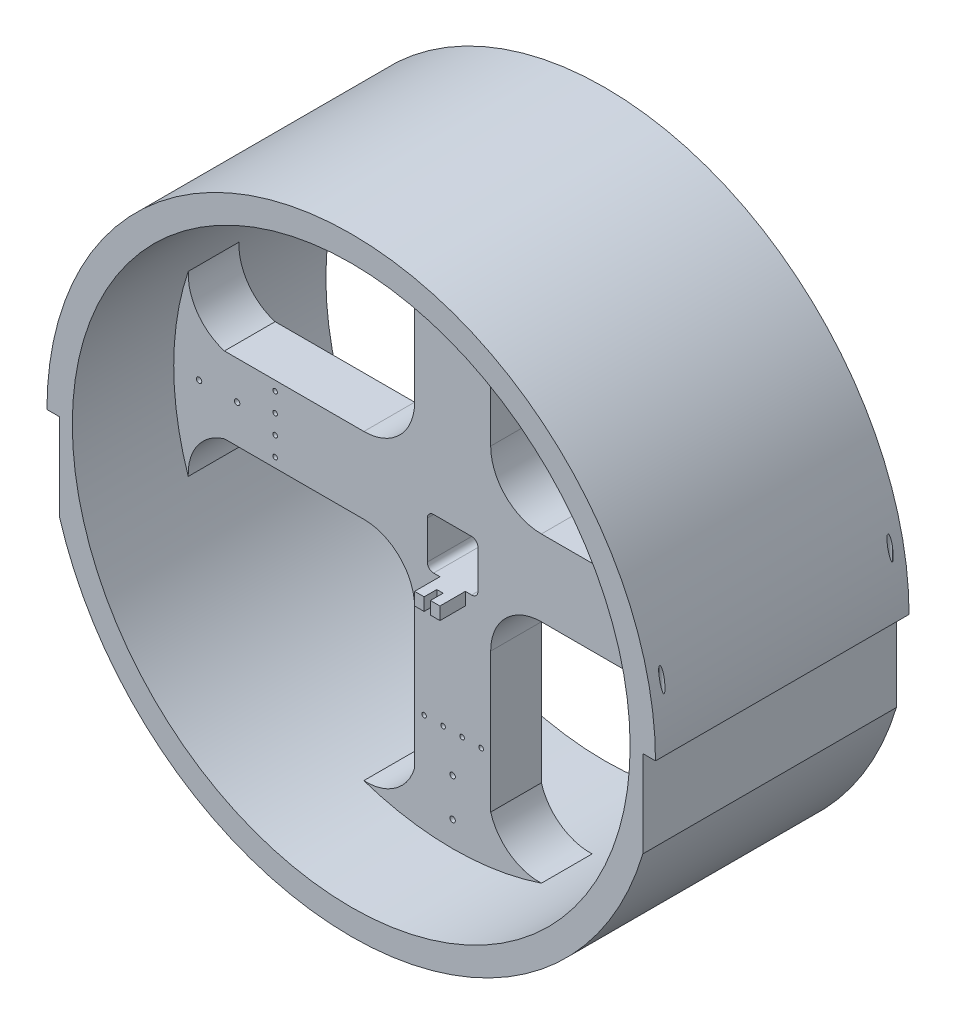
SolidWorks part; units mm, degrees
material "6061 Alloy"
ref_plane "Front Plane" through (0, 0, 0) normal (0, 0, 1) x (1, 0, 0)
ref_plane "Top Plane" through (0, 0, 0) normal (0, 1, 0) x (1, 0, 0)
ref_plane "Right Plane" through (0, 0, 0) normal (1, 0, 0) x (0, 0, -1)
sketch "Sketch1" plane through (0, 0, 0) normal (0, 0, 1) x (1, 0, 0)
  circle A0 centre (0, 0) radius 152.4
  circle A1 centre (0, 0) radius 139.7
  dimension "D1" = 304.8
  dimension "D2" = 279.4
extrude "Boss-Extrude1" add sketch "Sketch1" along normal mid plane 127
sketch "Sketch2" plane through (0, 0, 0) normal (0, 0, 1) x (1, 0, 0)
  line L0 (-114.3, 19.05) -> (-138.7192, 19.05)
  line L1 (-147.1918, -19.05) -> (147.1918, -19.05)
  line L2 (-147.1918, -19.05) -> (-147.1918, 19.05)
  line L3 (-147.1918, 19.05) -> (147.1918, 19.05)
  line L4 (147.1918, -19.05) -> (147.1918, 19.05)
  line L5 (-147.1918, -19.05) -> (147.1918, 19.05) construction
  line L6 (-147.1918, 19.05) -> (147.1918, -19.05) construction
  line L7 (19.05, -143.9568) -> (-19.05, -143.9568)
  line L8 (19.05, -143.9568) -> (19.05, 143.9568)
  line L9 (19.05, 143.9568) -> (-19.05, 143.9568)
  line L10 (-19.05, -143.9568) -> (-19.05, 143.9568)
  line L11 (19.05, -143.9568) -> (-19.05, 143.9568) construction
  line L12 (19.05, 143.9568) -> (-19.05, -143.9568) construction
  line L15 (-44.45, 19.05) -> (-19.05, 19.05)
  line L16 (-19.05, 44.45) -> (-19.05, 19.05)
  line L17 (-132.4254, 44.4927) -> (-143.3503, 19.05)
  line L18 (-143.3503, 19.05) -> (-138.7192, 19.05)
  line L19 (-138.7192, 19.05) -> (-143.3503, 19.05)
  line L20 (-19.05, 114.3) -> (-19.05, 143.9568)
  line L21 (-44.45, 132.4398) -> (-19.05, 143.9568)
  line L22 (44.45, 19.05) -> (19.05, 19.05)
  line L23 (19.05, 44.45) -> (19.05, 19.05)
  line L24 (19.05, 143.3503) -> (19.05, 138.7192)
  line L25 (19.05, 114.3) -> (19.05, 138.7192)
  line L26 (44.4927, 132.4254) -> (19.05, 143.3503)
  line L27 (114.3, 19.05) -> (143.9568, 19.05)
  line L28 (132.4398, 44.45) -> (143.9568, 19.05)
  line L29 (19.05, -44.45) -> (19.05, -19.05)
  line L30 (44.45, -19.05) -> (19.05, -19.05)
  line L31 (143.3503, -19.05) -> (138.7192, -19.05)
  line L32 (114.3, -19.05) -> (138.7192, -19.05)
  line L33 (132.4254, -44.4927) -> (143.3503, -19.05)
  line L34 (19.05, -114.3) -> (19.05, -143.9568)
  line L35 (44.45, -132.4398) -> (19.05, -143.9568)
  line L36 (-44.45, -19.05) -> (-19.05, -19.05)
  line L37 (-19.05, -44.45) -> (-19.05, -19.05)
  line L38 (-19.05, -143.3503) -> (-19.05, -138.7192)
  line L39 (-19.05, -114.3) -> (-19.05, -138.7192)
  line L40 (-44.4927, -132.4254) -> (-19.05, -143.3503)
  line L41 (-114.3, -19.05) -> (-143.9568, -19.05)
  line L42 (-132.4398, -44.45) -> (-143.9568, -19.05)
  arc A1 (-44.45, 19.05) -> (-19.05, 44.45) centre (-44.45, 44.45) ccw
  arc A2 (-114.3, 19.05) -> (-132.4254, 44.4927) centre (-107.0492, 43.3931) cw
  circle A3 centre (0, 0) radius 139.7 construction
  arc A5 (-19.05, 114.3) -> (-44.45, 132.4398) centre (-43.3968, 107.0616) ccw
  arc A6 (19.05, 44.45) -> (44.45, 19.05) centre (44.45, 44.45) ccw
  arc A7 (19.05, 114.3) -> (44.4927, 132.4254) centre (43.3931, 107.0492) cw
  arc A8 (114.3, 19.05) -> (132.4398, 44.45) centre (107.0616, 43.3968) ccw
  arc A9 (44.45, -19.05) -> (19.05, -44.45) centre (44.45, -44.45) ccw
  arc A10 (114.3, -19.05) -> (132.4254, -44.4927) centre (107.0492, -43.3931) cw
  arc A11 (19.05, -114.3) -> (44.45, -132.4398) centre (43.3968, -107.0616) ccw
  arc A12 (-19.05, -44.45) -> (-44.45, -19.05) centre (-44.45, -44.45) ccw
  arc A13 (-19.05, -114.3) -> (-44.4927, -132.4254) centre (-43.3931, -107.0492) cw
  arc A14 (-114.3, -19.05) -> (-132.4398, -44.45) centre (-107.0616, -43.3968) ccw
  point P0 (0, 0)
  point P6 (0, 0)
  point P67 (0, 0)
  dimension "D3" = 25.4
  dimension "D5" = 25.4
  dimension "D1" = 38.1
  dimension "D2" = 38.1
  dimension "D4" = 114.3
  dimension "D6" = 114.3
  dimension "D7" = 4
extrude "Boss-Extrude2" add sketch "Sketch2" along normal mid plane 25.4 contours L1 L10 L3 L2 | L10 L1 L8 L3 | L10 L3 L8 L9 | L8 L1 L4 L3 | L10 L7 L8 L1 | A14 L1 L42 | L10 A13 L40 | A11 L8 L35 | A9 L1 L8 | L1 A10 L33 | A8 L3 L28 | L8 A7 L26 | A5 L10 L21 | L0 A2 L17 L3 | A1 L3 L10 | A6 L8 L3 | A12 L10 L1 region at (-83.1209, 0, 0) region at (-132.2215, 26.1932, 0) region at (-24.7235, 24.7235, 0) region at (0, 81.5034, 0) region at (0, 0, 0) region at (24.7235, 24.7235, 0) region at (83.1209, 0, 0) region at (-24.7235, -24.7235, 0) region at (0, -81.5034, 0) region at (-26.2233, 132.4495, 0) region at (24.7235, -24.7235, 0) region at (-132.4495, -26.2233, 0) region at (132.4495, 26.2233, 0) region at (26.1932, 132.2215, 0) region at (-26.1932, -132.2215, 0) region at (132.2215, -26.1932, 0) region at (26.2233, -132.4495, 0)
sketch "Sketch4" plane through (0, 0, 0) normal (0, 0, 1) x (1, 0, 0)
  line L0 (-12.7, -24.892) -> (-12.7, 0.508)
  line L5 (-12.7, -24.892) -> (12.7, -24.892)
  line L6 (-12.7, 0.508) -> (12.7, 0.508)
  line L7 (12.7, -24.892) -> (12.7, 0.508)
  line L8 (-12.7, -24.892) -> (12.7, 0.508) construction
  line L9 (-12.7, 0.508) -> (12.7, -24.892) construction
  point P1 (0, -12.192)
  dimension "D1" = 25.4
  dimension "D2" = 25.4
  dimension "D3" = 0
  dimension "D4" = 0.508
extrude "Cut-Extrude3" cut sketch "Sketch4" against normal through all both and the other way through all
sketch "Sketch8" plane through (0, 0, 63.5) normal (0, 0, 1) x (1, 0, 0)
  line L0 (-146.05, 0) -> (-163.2527, 0)
  line L1 (-146.05, 0) -> (-146.05, -50.8)
  line L2 (-163.2527, 0) -> (-163.2527, -50.8)
  line L3 (-146.05, -50.8) -> (-163.2527, -50.8)
  circle A0 centre (0, 0) radius 152.4 construction
  dimension "D1" = 50.8
  dimension "D2" = 146.05
extrude "Cut-Extrude5" cut sketch "Sketch8" against normal through all
hole_wizard "#4-40 Tapped Hole2" positions "Sketch21" profile "Sketch22" tap size "#4-40" standard "ANSI Inch" end condition through all
sketch "Sketch21" plane through (0, 0, 0) normal (0, -1, 0) x (-1, 0, 0)
  line L0 (146.05, -63.5) -> (152.4, -63.5) construction
  line L1 (146.05, 63.5) -> (152.4, 63.5) construction
  line L2 (152.4, 63.5) -> (152.4, -63.5) construction
  point P0 (149.225, 57.15)
  point P2 (149.225, -57.15)
  dimension "D1" = 6.35
  dimension "D2" = 6.35
  dimension "D3" = 3.175
  dimension "D4" = 3.175
sketch "Sketch22" plane through (-149.225, 0, -57.15) normal (1, 0, 0) x (0, 0, -1)
  line L0 (0, 0) -> (0, 152.4)
  line L1 (0, 152.4) -> (1.1303, 152.4)
  line L2 (1.1303, 152.4) -> (1.1303, 0)
  line L5 (1.1303, 0) -> (0, 0)
  line L11 (0, -6.35) -> (0, 107.95) construction
  dimension "Thru Tap Drill Dia." = 2.2606
  dimension "Thru Tap Drill Depth" = 152.4
cosmetic thread "Hole Thread7" parameters "D2"=2.8448
cosmetic thread "Hole Thread8" parameters "D2"=2.8448
mirror "Mirror1" about plane through (0, 0, 0) normal (1, 0, 0) of "#4-40 Tapped Hole2", "Cut-Extrude5"
hole_wizard "#4-40 Tapped Hole1" positions "Sketch11" profile "Sketch12" tap size "#4-40" standard "ANSI Inch" end condition through all
sketch "Sketch11" plane through (0, 0, 12.7) normal (0, 0, 1) x (1, 0, 0)
  line L1 (44.45, 19.05) -> (114.3, 19.05) construction
  point P4 (88.9, 14.2875)
  point P6 (88.9, 4.7625)
  point P17 (88.9, -4.7625)
  point P19 (88.9, -14.2875)
  dimension "D1" = 88.9
  dimension "D2" = 88.9
  dimension "D3" = 88.9
  dimension "D4" = 9.525
  dimension "D5" = 88.9
  dimension "D6" = 9.525
  dimension "D7" = 4.7625
  dimension "D8" = 9.525
sketch "Sketch12" plane through (88.9, 14.2875, 12.7) normal (1, 0, 0) x (0, -1, 0)
  line L0 (0, 0) -> (0, 76.2)
  line L1 (0, 76.2) -> (1.1303, 76.2)
  line L2 (1.1303, 76.2) -> (1.1303, 0)
  line L5 (1.1303, 0) -> (0, 0)
  line L11 (0, -6.35) -> (0, 107.95) construction
  dimension "Thru Tap Drill Dia." = 2.2606
  dimension "Thru Tap Drill Depth" = 76.2
cosmetic thread "Hole Thread1" parameters "D2"=2.8448
cosmetic thread "Hole Thread2" parameters "D2"=2.8448
cosmetic thread "Hole Thread3" parameters "D2"=2.8448
cosmetic thread "Hole Thread4" parameters "D2"=2.8448
hole_wizard "#6-32 Tapped Hole1" positions "Sketch13" profile "Sketch14" tap size "#6-32" standard "ANSI Inch" end condition through all
sketch "Sketch13" plane through (0, 0, 12.7) normal (0, 0, 1) x (1, 0, 0)
  point P0 (-107.95, 0)
  point P2 (-127, 0)
  dimension "D1" = 107.95
  dimension "D2" = 19.05
sketch "Sketch14" plane through (-107.95, 0, 12.7) normal (1, 0, 0) x (0, -1, 0)
  line L0 (0, 0) -> (0, 76.2)
  line L1 (0, 76.2) -> (1.3525, 76.2)
  line L2 (1.3525, 76.2) -> (1.3525, 0)
  line L5 (1.3525, 0) -> (0, 0)
  line L11 (0, -6.35) -> (0, 107.95) construction
  dimension "Thru Tap Drill Dia." = 2.7051
  dimension "Thru Tap Drill Depth" = 76.2
cosmetic thread "Hole Thread5" parameters "D2"=3.5052
cosmetic thread "Hole Thread6" parameters "D2"=3.5052
pattern_circular "CirPattern1" count 4 every 90 about axis through (0, 0, 63.5) along (0, 0, 1) of "#6-32 Tapped Hole1"
sketch "Sketch17" plane through (0, 0, 12.7) normal (0, 0, 1) x (1, 0, 0)
  line L0 (-12.7, -24.892) -> (12.7, -24.892) construction
  line L1 (-12.7, 0.508) -> (-12.7, -24.892) construction
  line L2 (-12.7, -21.717) -> (-12.7, -24.892)
  line L3 (-12.7, -24.892) -> (-9.525, -24.892)
  line L4 (12.7, 0.508) -> (-12.7, 0.508) construction
  line L5 (12.7, -24.892) -> (12.7, 0.508) construction
  line L6 (-12.7, -2.667) -> (-12.7, 0.508)
  line L7 (-12.7, 0.508) -> (-9.525, 0.508)
  line L8 (9.525, 0.508) -> (12.7, 0.508)
  line L9 (12.7, 0.508) -> (12.7, -2.667)
  line L10 (12.7, -21.717) -> (12.7, -24.892)
  line L11 (12.7, -24.892) -> (9.525, -24.892)
  arc A0 (-9.525, -24.892) -> (-12.7, -21.717) centre (-9.525, -21.717) cw
  arc A1 (-12.7, -2.667) -> (-9.525, 0.508) centre (-9.525, -2.667) cw
  arc A2 (9.525, 0.508) -> (12.7, -2.667) centre (9.525, -2.667) cw
  arc A3 (9.525, -24.892) -> (12.7, -21.717) centre (9.525, -21.717) ccw
  dimension "D1" = 3.175
  dimension "D4" = 3.175
  dimension "D5" = 3.175
  dimension "D6" = 3.175
  dimension "D12" = 3.175
  dimension "D2" = 3.175
  dimension "D3" = 3.175
  dimension "D7" = 3.175
  dimension "D8" = 3.175
  dimension "D9" = 3.175
  dimension "D10" = 3.175
  dimension "D11" = 3.175
  dimension "D13" = 0
extrude "Boss-Extrude4" add sketch "Sketch17" against normal up to surface (25.4 mm away) up to face at (1.3525, 107.95, -12.7)
sketch "Sketch18" plane through (0, 0, 12.7) normal (0, 0, 1) x (1, 0, 0)
  line L0 (-9.525, -24.892) -> (9.525, -24.892) construction
  line L1 (-6.35, -24.892) -> (6.35, -24.892)
  line L2 (-6.35, -24.892) -> (-6.35, -31.242)
  line L3 (-6.35, -31.242) -> (6.35, -31.242)
  line L4 (6.35, -24.892) -> (6.35, -31.242)
  line L5 (-12.7, -2.667) -> (-12.7, -21.717) construction
  dimension "D1" = 12.7
  dimension "D2" = 6.35
  dimension "D3" = 6.35
extrude "Boss-Extrude5" add sketch "Sketch18" along normal blind 12.7 and the other way blind 38.1
sketch "Sketch19" plane through (0, -24.892, 0) normal (0, 1, 0) x (1, 0, 0)
  line L0 (6.35, -25.4) -> (-6.35, -25.4) construction
  line L1 (-1.5875, -25.4) -> (1.5875, -25.4)
  line L2 (-1.5875, -25.4) -> (-1.5875, -19.05)
  line L3 (-1.5875, -19.05) -> (1.5875, -19.05)
  line L4 (1.5875, -25.4) -> (1.5875, -19.05)
  line L5 (-6.35, -12.7) -> (-6.35, -25.4) construction
  dimension "D1" = 3.175
  dimension "D2" = 4.7625
  dimension "D3" = 6.35
extrude "Cut-Extrude6" cut sketch "Sketch19" against normal up to next
sketch "Sketch20" plane through (0, -24.892, 0) normal (0, 1, 0) x (1, 0, 0)
  line L0 (6.35, 25.4) -> (-6.35, 25.4) construction
  line L1 (1.5875, 25.4) -> (-1.5875, 25.4)
  line L2 (1.5875, 25.4) -> (1.5875, 19.05)
  line L3 (1.5875, 19.05) -> (-1.5875, 19.05)
  line L4 (-1.5875, 25.4) -> (-1.5875, 19.05)
  line L5 (6.35, 25.4) -> (6.35, 12.7) construction
  dimension "D1" = 3.175
  dimension "D2" = 6.35
  dimension "D3" = 4.7625
extrude "Cut-Extrude7" cut sketch "Sketch20" against normal up to next
pattern_circular "CirPattern2" count 4 every 90 about axis through (0, 0, 63.5) along (0, 0, 1) of "#4-40 Tapped Hole1"
